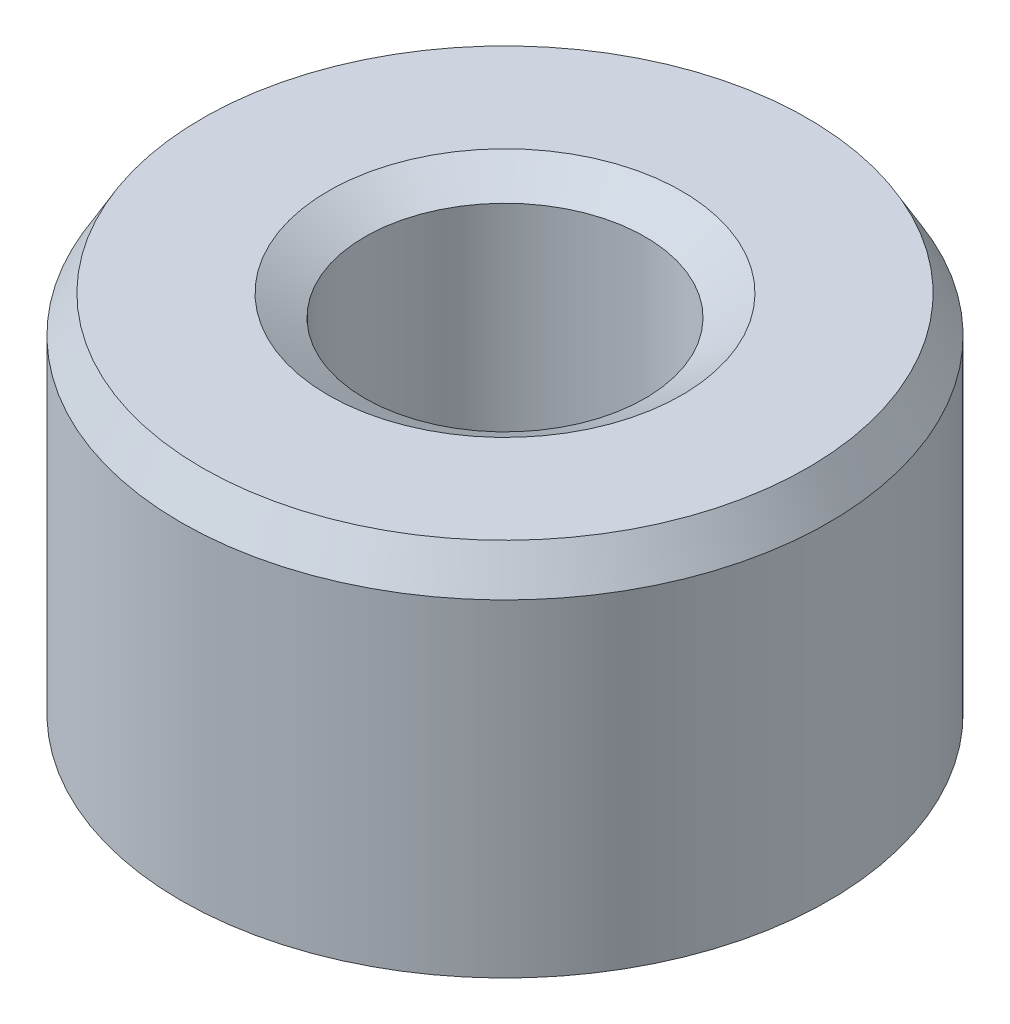
SolidWorks part; units mm, degrees
ref_plane "Front Plane" through (0, 0, 0) normal (0, 0, 1) x (1, 0, 0)
ref_plane "Top Plane" through (0, 0, 0) normal (0, 1, 0) x (1, 0, 0)
ref_plane "Right Plane" through (0, 0, 0) normal (1, 0, 0) x (0, 0, -1)
sketch "Sketch1" plane through (0, 0, 0) normal (0, 1, 0) x (1, 0, 0)
  circle A0 centre (0, 0) radius 17.5
  dimension "SLEEVE_OD" = 35
extrude "Boss-Extrude1" add sketch "Sketch1" along normal blind 20.8153
sketch "Sketch2" plane through (0, 0, 0) normal (0, 1, 0) x (1, 0, 0)
  circle A0 centre (0, 0) radius 7.5661
  dimension "BORE_D" = 15.1322
extrude "Cut-Extrude1" cut sketch "Sketch2" along normal through all
chamfer "Chamfer1" distance 1.9838 angle 30 4 edges at (0, 20.8153, 7.5661) (0, 0, 7.5661) (0, 0, 17.5) (0, 20.8153, 17.5) first distance on face at (0, 20.8153, 7.5661) first distance on face at (0, 0, 7.5661) first distance on face at (0, 20.8153, 17.5)
